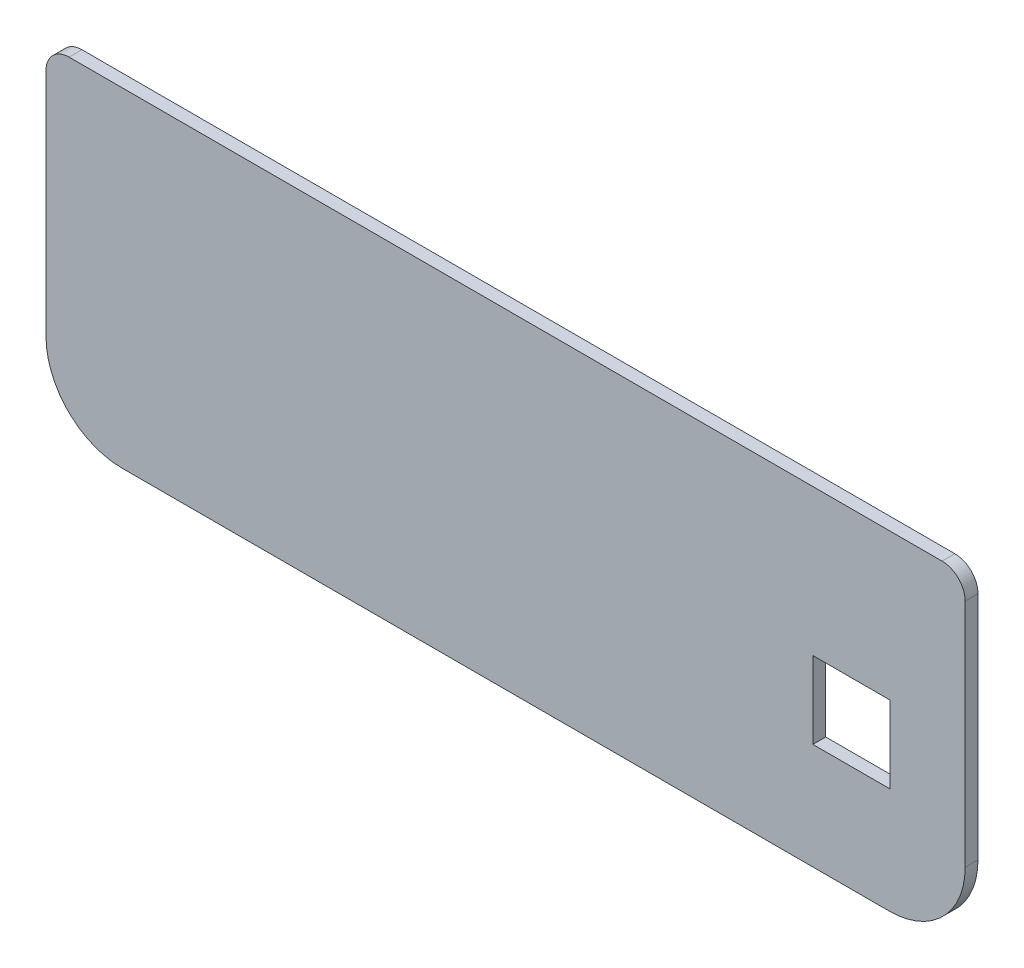
SolidWorks part; units mm, degrees
ref_plane "Plan de face" through (0, 0, 0) normal (0, 0, 1) x (1, 0, 0)
ref_plane "Plan de dessus" through (0, 0, 0) normal (0, 1, 0) x (1, 0, 0)
ref_plane "Plan de droite" through (0, 0, 0) normal (1, 0, 0) x (0, 0, -1)
sketch "Esquisse20" plane through (0, 0, 0) normal (0, 0, 1) x (1, 0, 0)
  line L1 (14.8, -2) -> (164.37, -2)
  line L2 (0, 12.8) -> (0, 57.73)
  line L3 (4.5, 62.23) -> (174.67, 62.23)
  line L4 (179.17, 12.8) -> (179.17, 57.73)
  arc A0 (0, 57.73) -> (4.5, 62.23) centre (4.5, 57.73) cw
  arc A1 (174.67, 62.23) -> (179.17, 57.73) centre (174.67, 57.73) cw
  arc A2 (164.37, -2) -> (179.17, 12.8) centre (164.37, 12.8) ccw
  arc A3 (14.8, -2) -> (0, 12.8) centre (14.8, 12.8) cw
  point P7 (0, 62.23)
  point P10 (179.17, 62.23)
  point P14 (179.17, -2)
  point P17 (0, -2)
extrude "Boss.-Extru.1" add sketch "Esquisse20" along normal blind 2.5
sketch "Esquisse21" plane through (0, 0, 0) normal (0, 0, -1) x (-1, 0, 0)
  line L1 (-164.4848, 18.702) -> (-149.4848, 18.702)
  line L2 (-164.4848, 18.702) -> (-164.4848, 33.702)
  line L3 (-164.4848, 33.702) -> (-149.4848, 33.702)
  line L4 (-149.4848, 18.702) -> (-149.4848, 33.702)
  dimension "D1" = 15
  dimension "D2" = 15
extrude "Enlèv. mat.-Extru.1" cut sketch "Esquisse21" against normal blind 10
